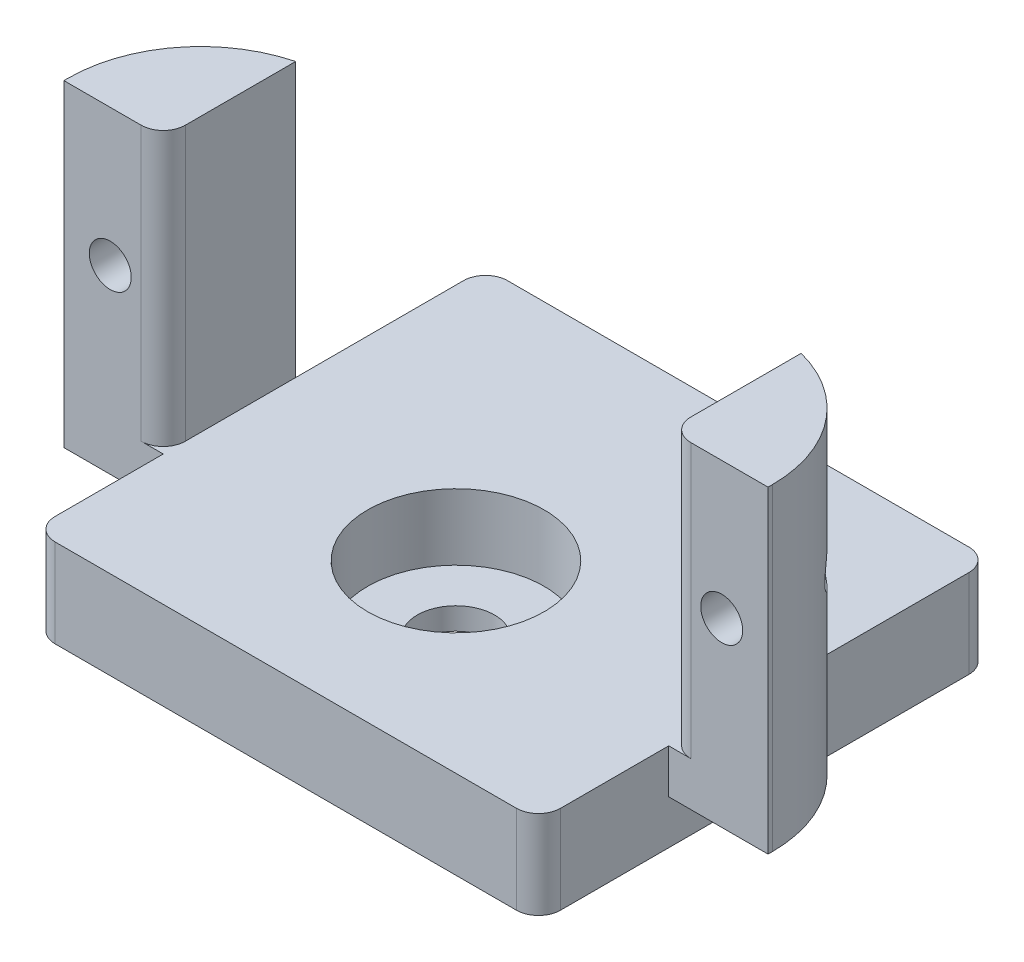
SolidWorks part; units mm, degrees
ref_plane "前视基准面" through (0, 0, 0) normal (0, 0, 1) x (1, 0, 0)
ref_plane "上视基准面" through (0, 0, 0) normal (0, 1, 0) x (1, 0, 0)
ref_plane "右视基准面" through (0, 0, 0) normal (1, 0, 0) x (0, 0, -1)
other "Configuration Table"
sketch "草图1" plane through (0, 0, 0) normal (0, 1, 0) x (1, 0, 0)
  line L0 (11.45, 10.5) -> (11.45, -10.5)
  line L1 (11.45, 10.5) -> (-11.45, 10.5)
  line L2 (11.45, -10.5) -> (-11.45, -10.5)
  line L3 (-11.45, 10.5) -> (-11.45, -10.5)
  line L4 (11.45, 10.5) -> (-11.45, -10.5) construction
  line L5 (11.45, -10.5) -> (-11.45, 10.5) construction
  point P1 (0, 0)
  dimension "D1" = 21
  dimension "D2" = 22.9
extrude "凸台-拉伸1" add sketch "草图1" along normal blind 2
sketch "草图2" plane through (0, 0, 0) normal (0, 1, 0) x (1, 0, 0)
  line L0 (-11.45, -10.5) -> (-11.45, -4.1) construction
  line L1 (-11.45, 10.5) -> (-11.45, -10.5) construction
  line L2 (-11.45, -4.1) -> (-15.95, -4.1)
  line L3 (-15.95, -4.1) -> (-15.95, 1.9)
  line L4 (-15.95, 1.9) -> (-11.45, 1.9)
  line L5 (-11.45, 1.9) -> (-11.45, -4.1)
  line L6 (11.45, -4.1) -> (15.95, -4.1)
  line L7 (11.45, -10.5) -> (11.45, 10.5) construction
  line L8 (15.95, -4.1) -> (15.95, 1.9)
  line L9 (15.95, 1.9) -> (11.45, 1.9)
  line L10 (11.45, 1.9) -> (11.45, -4.1)
  dimension "D1" = 6.4
  dimension "D2" = 4.5
  dimension "D3" = 6
  dimension "D4" = 4.5
  dimension "D5" = 6
extrude "凸台-拉伸2" add sketch "草图2" along normal blind 14.4
fillet "圆角1" radius 1 2 edges at (11.45, 8.2, 4.1) (-11.45, 8.2, 4.1)
sketch "草图3" plane through (0, 2, 0) normal (0, 1, 0) x (1, 0, 0)
  line L0 (-0.63, -1.66) -> (-0.63, -10.5) construction
  line L5 (-11.45, -10.5) -> (11.45, -10.5) construction
  line L6 (-0.63, -1.66) -> (-11.45, -1.66) construction
  circle A0 centre (-0.63, -1.66) radius 4
  dimension "D3" = 8
extrude "切除-拉伸1" cut sketch "草图3" against normal blind 14.4
sketch "草图5" plane through (0, 0, 4.1) normal (0, 0, 1) x (1, 0, 0)
  line L0 (-11.45, 2) -> (-11.45, 8.2) construction
  line L4 (-11.45, 14.4) -> (-11.45, 2) construction
  line L5 (-11.45, 8.2) -> (-13.85, 8.2) construction
  line L6 (11.45, 2) -> (11.45, 8.2) construction
  line L8 (11.45, 2) -> (11.45, 14.4) construction
  line L9 (11.45, 8.2) -> (13.85, 8.2) construction
  circle A0 centre (-13.85, 8.2) radius 0.95
  circle A1 centre (13.85, 8.2) radius 0.95
  dimension "D3" = 1.9
  dimension "D6" = 1.9
  dimension "D1" = 6.2
  dimension "D2" = 2.4
  dimension "D4" = 6.2
  dimension "D5" = 2.4
extrude "切除-拉伸2" cut sketch "草图5" against normal blind 14.4
extrude "凸台-拉伸3" add sketch "草图1<2>" against normal blind 2
sketch "草图1<2>" plane through (0, 0, 0) normal (0, 1, 0) x (1, 0, 0) same geometry as "草图1"
sketch "草图6" plane through (0, 0, 0) normal (0, 1, 0) x (1, 0, 0)
  circle A2 centre (-0.63, -1.66) radius 4
  dimension "D1" = 8
extrude "切除-拉伸3" cut sketch "草图6" against normal blind 1
sketch "草图7" plane through (0, -1, 0) normal (0, 1, 0) x (1, 0, 0)
  circle A0 centre (-0.63, -1.66) radius 1.75
  dimension "D1" = 3.5
extrude "切除-拉伸4" cut sketch "草图7" against normal blind 1
fillet "圆角2" radius 1 2 edges at (11.45, 0, -10.5) (-11.45, 0, -10.5)
sketch "草图8" plane through (0, 2, 0) normal (0, 1, 0) x (1, 0, 0)
sketch "草图9" plane through (0, 2, 0) normal (0, 1, 0) x (1, 0, 0)
  line L5 (-11.4506, -10.5) -> (-11.4506, -10)
  line L6 (-11.4506, -10) -> (11.45, -10)
  line L7 (11.45, -10) -> (11.45, -10.5)
  line L8 (-11.4506, -10.5) -> (11.45, -10.5)
  dimension "D1" = 0.5
extrude "切除-拉伸5" cut sketch "草图9" against normal blind 4
fillet "圆角4" radius 1 2 edges at (11.45, 0, 10) (-11.45, 0, 10)
fillet "圆角5" radius 6 2 edges at (15.95, 7.2, -1.9) (-15.95, 7.2, -1.9)
